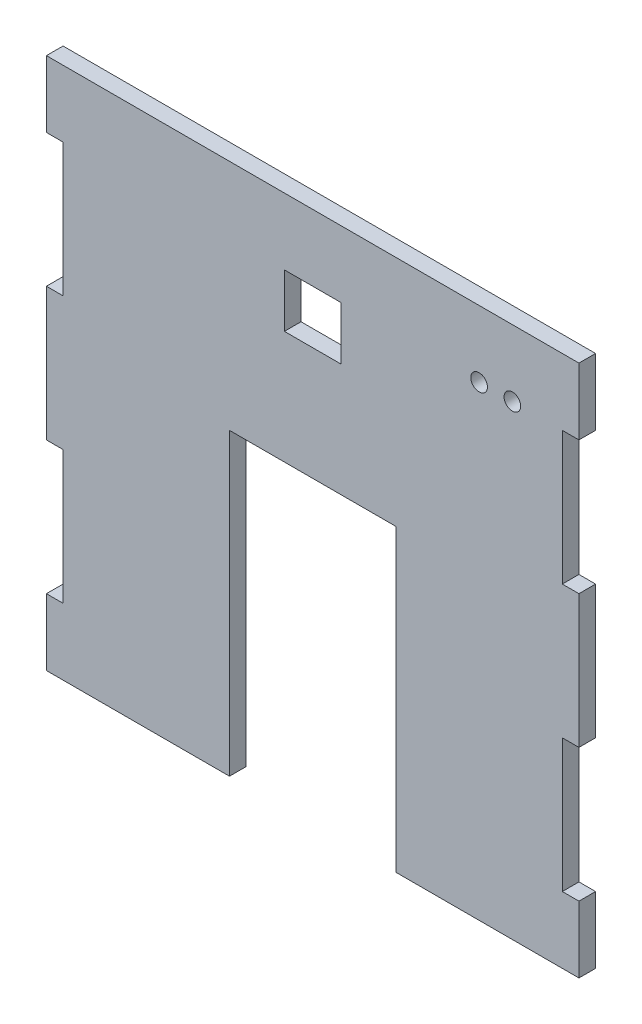
SolidWorks part; units mm, degrees
ref_plane "Front Plane" through (0, 0, 0) normal (0, 0, 1) x (1, 0, 0)
ref_plane "Top Plane" through (0, 0, 0) normal (0, 1, 0) x (1, 0, 0)
ref_plane "Right Plane" through (0, 0, 0) normal (1, 0, 0) x (0, 0, -1)
sketch "Sketch1" plane through (0, 0, 0) normal (0, 0, 1) x (1, 0, 0)
  line L0 (0, 10) -> (0, 80) construction
  line L1 (-80, 80) -> (80, 80)
  line L2 (-80, 80) -> (-80, -80)
  line L3 (-80, -80) -> (80, -80)
  line L4 (80, 80) -> (80, -80)
  line L5 (-80, 80) -> (80, -80) construction
  line L6 (-80, -80) -> (80, 80) construction
  line L7 (-25, -80) -> (25, -80)
  line L8 (-25, -80) -> (-25, 10)
  line L9 (-25, 10) -> (25, 10)
  line L10 (25, -80) -> (25, 10)
  line L11 (80, 60) -> (-80, 60) construction
  line L12 (0, 80) -> (0, 60) construction
  line L13 (-8.5, 60) -> (8.5, 60)
  line L14 (-8.5, 60) -> (-8.5, 44)
  line L15 (-8.5, 44) -> (8.5, 44)
  line L16 (8.5, 60) -> (8.5, 44)
  circle A0 centre (50, 60) radius 2.5
  circle A1 centre (60, 60) radius 2.5
  point P0 (0, 0)
  dimension "D6" = 5
  dimension "D1" = 160
  dimension "D2" = 160
  dimension "D3" = 90
  dimension "D4" = 50
  dimension "D5" = 20
  dimension "D7" = 10
  dimension "D8" = 20
  dimension "D9" = 17
  dimension "D10" = 16
extrude "Boss-Extrude1" add sketch "Sketch1" along normal blind 5 contours L10 L3 L4 L1 L2 L8 L9 A1 A0 L13 L16 L15 L14 region at (0, 77.7373, 0)
sketch "Sketch2" plane through (0, 0, 5) normal (0, 0, 1) x (1, 0, 0)
  line L0 (-80, -60) -> (-75, -60)
  line L1 (-80, 80) -> (-80, -80) construction
  line L2 (-75, -60) -> (-75, -20)
  line L3 (-75, -20) -> (-80, -20)
  line L4 (-80, -20) -> (-80, 20)
  line L5 (-80, 20) -> (-75, 20)
  line L6 (-75, 20) -> (-75, 60)
  line L7 (-75, 60) -> (-80, 60)
  line L8 (-80, 60) -> (-80, -60)
  line L9 (-75, 20) -> (-75, -20) construction
  line L10 (-75, 0) -> (80, 0) construction
  line L11 (80, 80) -> (80, -80) construction
  line L12 (80, 60) -> (75, 60)
  line L13 (75, 60) -> (75, 20)
  line L14 (75, 20) -> (80, 20)
  line L15 (80, 20) -> (80, -20)
  line L16 (80, -20) -> (75, -20)
  line L17 (75, -20) -> (75, -60)
  line L18 (75, -60) -> (80, -60)
  line L19 (80, -60) -> (80, 60)
  line L20 (75, 20) -> (75, -20) construction
  line L21 (75, 0) -> (-80, 0) construction
  line M21 (80, -80) -> (80, 80)
  line M23 (-80, 80) -> (-80, -80)
  dimension "D1" = 40
  dimension "D2" = 40
  dimension "D3" = 5
  dimension "D4" = 40
  dimension "D5" = 5
  dimension "D6" = 40
extrude "Cut-Extrude1" cut sketch "Sketch2" against normal through all contours L6 L7 L5 M23 | L2 L3 L0 M23 | L17 L18 L16 M21 | L13 L14 L12 M21 | L19 L12 L13 L14 L15 L16 L17 L18 region at (-77.5, -40, 5) region at (-77.5, 40, 5) region at (77.5, 40, 5) region at (77.5, -40, 5)
